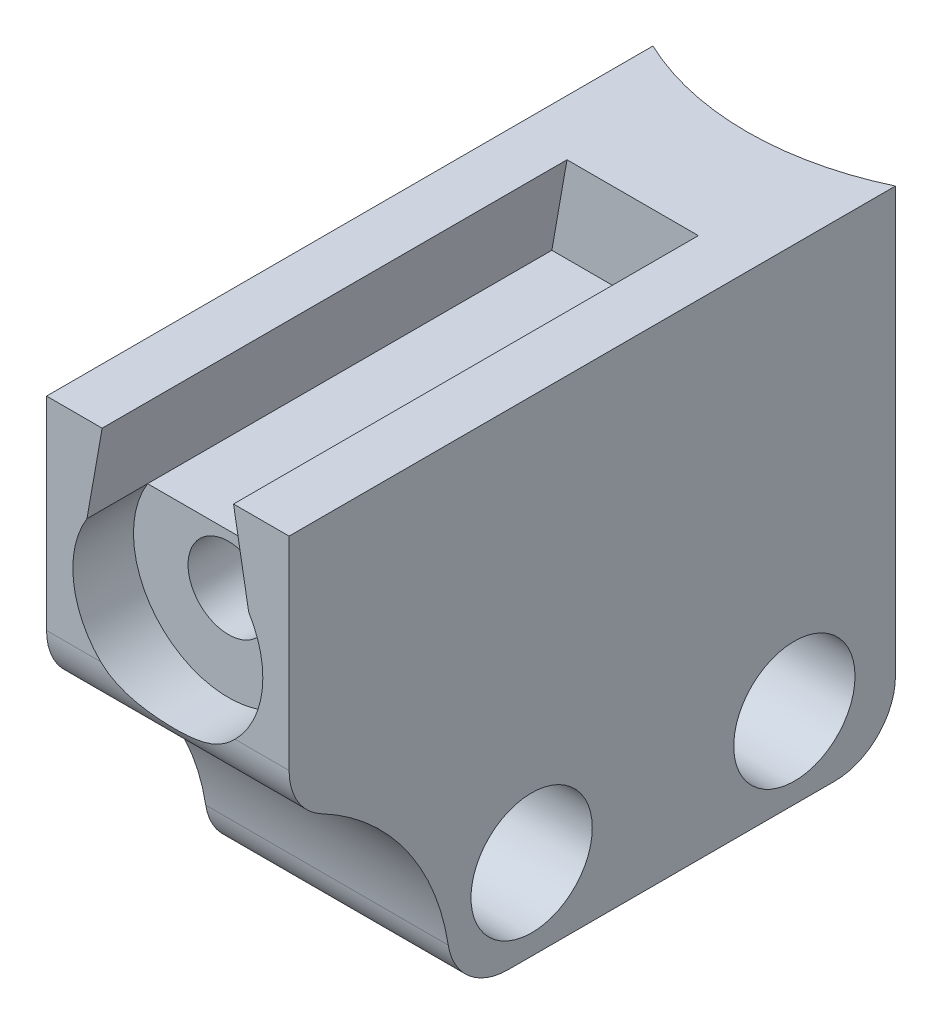
SolidWorks part; units mm, degrees
ref_plane "Front Plane" through (0, 0, 0) normal (0, 0, 1) x (1, 0, 0)
ref_plane "Top Plane" through (0, 0, 0) normal (0, 1, 0) x (1, 0, 0)
ref_plane "Right Plane" through (0, 0, 0) normal (1, 0, 0) x (0, 0, -1)
sketch "Sketch1" plane through (0, 0, 0) normal (1, 0, 0) x (0, 0, -1)
  line L0 (-17.0163, 0) -> (23.5429, 0) construction
  line L1 (0, 20.1404) -> (0, -15.6882) construction
  line L3 (-15, 12) -> (15, 12)
  line L4 (-15, 12) -> (-15, 0)
  line L5 (-7, -12) -> (15, -12)
  line L6 (15, 12) -> (15, -12)
  arc A0 (-15, 0) -> (-7, -12) centre (-18.9807, -11.3205) cw
  circle A1 centre (-3, -8) radius 3
  circle A2 centre (10, -8) radius 3
  point P17 (14.0589, -3.229)
  dimension "D3" = 12
  dimension "D4" = 6
  dimension "D1" = 30
  dimension "D2" = 24
  dimension "D5" = 13
  dimension "D6" = 5
  dimension "D7" = 4
  dimension "D8" = 8
extrude "Boss-Extrude1" add sketch "Sketch1" along normal mid plane 12
fillet "Fillet1" radius 3 3 edges at (0, -12, -15) (0, -12, 7) (0, 0, 15)
sketch "Sketch2" plane through (0, 0, 15) normal (0, 0, 1) x (1, 0, 0)
  line L0 (0, 12) -> (0, -1.0716) construction
  line L1 (6, 12) -> (-6, 12) construction
  line L2 (-3.25, 12) -> (-4, 7.7465)
  line L3 (-4, 7.7465) -> (4, 7.7465)
  line L4 (4, 7.7465) -> (3.25, 12)
  line L5 (-3.25, 12) -> (3.25, 12)
  arc A1 (-4, 7.7465) -> (4, 7.7465) centre (0, 5.2787) ccw
  circle A2 centre (0, 5.2787) radius 2
  line M7 (-6, 1.9561) -> (6, 1.9561)
  line M9 (6, 12) -> (-6, 12)
  dimension "D4" = 4.7
  dimension "D5" = 4
  dimension "D1" = 6.5
  dimension "D2" = 8
  dimension "D3" = 80
extrude "Cut-Extrude1" cut sketch "Sketch2" against normal through all contours A2 L0 | L0 A2 region at (0.8488, 5.2787, 15) region at (-0.8488, 5.2787, 15)
extrude "Cut-Extrude2" cut sketch "Sketch2<3>" against normal blind 23 contours L0 L5 L2 L3 | L0 L3 L4 M9 region at (1.819, 9.7999, 15) region at (-1.819, 9.7999, 15)
sketch "Sketch2<3>" plane through (0, 0, 15) normal (0, 0, 1) x (1, 0, 0) same geometry as "Sketch2"
extrude "Cut-Extrude3" cut sketch "Sketch2<4>" against normal blind 3 contours L0 L3 A1 A2 M7 | L3 L0 A2 A1 M7 | L0 A1 M7 | L0 A1 M7 region at (2.6383, 4.7992, 15) region at (-2.6383, 4.7992, 15) region at (-1.2751, 1.3976, 15) region at (1.2751, 1.3976, 15)
sketch "Sketch2<4>" plane through (0, 0, 15) normal (0, 0, 1) x (1, 0, 0) same geometry as "Sketch2"
sketch "Sketch3" plane through (0, 12, 0) normal (0, 1, 0) x (1, 0, 0)
  line L0 (-6, 15) -> (6, 15)
  arc A0 (-6, 15) -> (6, 15) centre (0, 27.6491) ccw
  line M7 (6, 15) -> (-6, 15)
  dimension "D1" = 14
extrude "Cut-Extrude4" cut sketch "Sketch3" against normal through all contours A0 M7 region at (0, 12, -14.4573)
